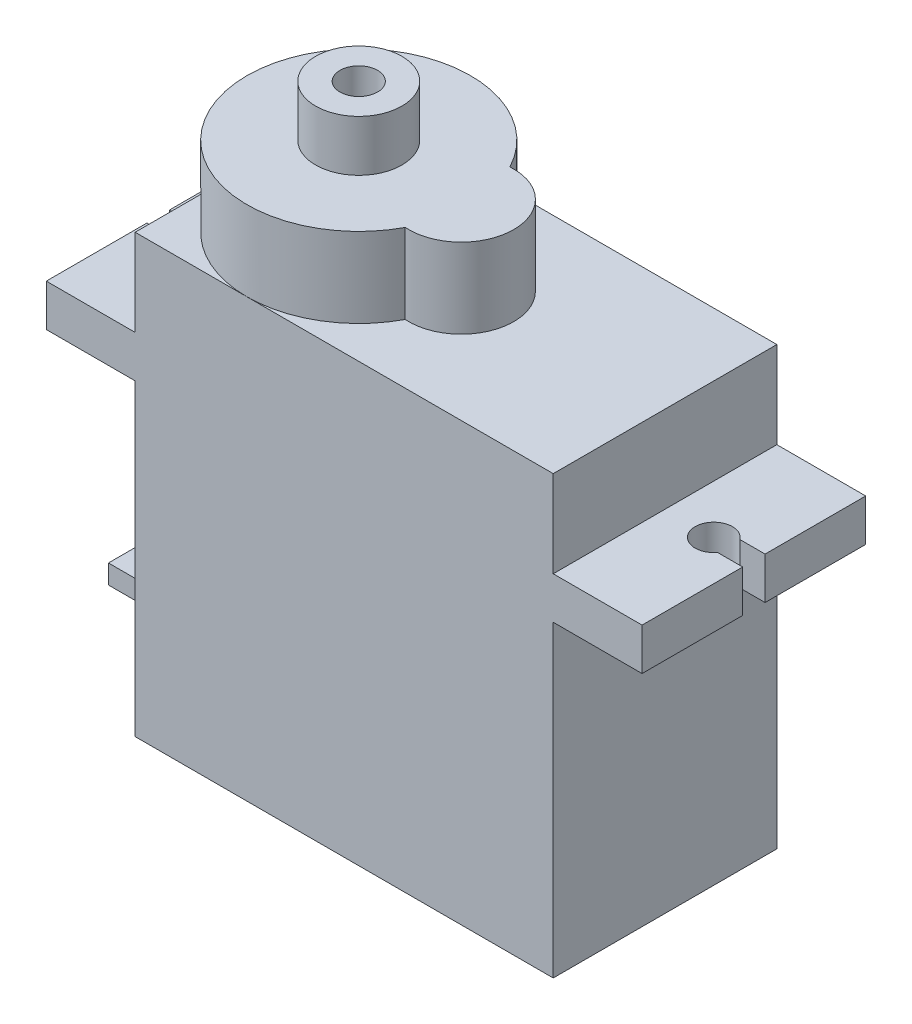
SolidWorks part; units mm, degrees
ref_plane "Front Plane" through (0, 0, 0) normal (0, 0, 1) x (1, 0, 0)
ref_plane "Top Plane" through (0, 0, 0) normal (0, 1, 0) x (1, 0, 0)
ref_plane "Right Plane" through (0, 0, 0) normal (1, 0, 0) x (0, 0, -1)
sketch "Sketch1" plane through (0, 0, 0) normal (0, 1, 0) x (1, 0, 0)
  line L1 (0, 0) -> (22.7711, 0)
  line L2 (0, 0) -> (0, 12.18)
  line L3 (0, 12.18) -> (22.7711, 12.18)
  line L4 (22.7711, 0) -> (22.7711, 12.18)
  dimension "D1" = 12.18
  dimension "D2" = 22.7711
extrude "Boss-Extrude1" add sketch "Sketch1" along normal blind 23.79
ref_plane "Plane1" through (0, 19.0656, 0) normal (0, 1, 0) x (1, 0, 0)
sketch "Sketch3" plane through (0, 19.0656, 0) normal (0, 1, 0) x (1, 0, 0)
  line L0 (22.7711, 12.18) -> (0, 12.18) construction
  line L1 (-4.8387, 0) -> (27.6098, 0)
  line L2 (-4.8387, 0) -> (-4.8387, 12.18)
  line L3 (-4.8387, 12.18) -> (27.6098, 12.18)
  line L4 (27.6098, 0) -> (27.6098, 12.18)
  line L5 (0, 0) -> (22.7711, 0) construction
  point P6 (11.3856, 0)
  point P9 (11.3856, 0)
  dimension "D1" = 32.4485
extrude "Boss-Extrude2" add sketch "Sketch3" against normal blind 2.286
sketch "Sketch4" plane through (0, 19.0656, 0) normal (0, 1, 0) x (1, 0, 0)
  line L0 (-3.4671, 6.6996) -> (-3.4671, 5.4804) construction
  line L1 (-4.8387, 6.6996) -> (-3.4671, 6.6996)
  line L2 (-4.8387, 12.18) -> (-4.8387, 0) construction
  line L3 (-3.4671, 5.4804) -> (-4.8387, 5.4804)
  line L4 (-1.6383, 6.09) -> (-1.6383, 8.3545) construction
  line L5 (11.3856, 12.18) -> (11.3856, 0) construction
  line L6 (22.7711, 12.18) -> (0, 12.18) construction
  line L7 (0, 0) -> (22.7711, 0) construction
  line L8 (24.4094, 6.09) -> (24.4094, 8.3545) construction
  line L9 (26.2382, 6.6996) -> (26.2382, 5.4804) construction
  line L10 (26.2382, 5.4804) -> (27.6098, 5.4804)
  line L11 (27.6098, 6.6996) -> (26.2382, 6.6996)
  line L12 (-4.8387, 6.6996) -> (-4.8387, 5.4804)
  line L13 (27.6098, 6.6996) -> (27.6098, 5.4804)
  arc A0 (-3.4671, 6.6996) -> (-3.4671, 5.4804) centre (-2.6543, 6.09) cw
  arc A1 (26.2382, 6.6996) -> (26.2382, 5.4804) centre (25.4254, 6.09) ccw
  point P6 (-3.4671, 6.09)
  point P8 (-4.8387, 6.09)
  dimension "D1" = 1.016
  dimension "D2" = 3.2004
  dimension "D3" = 1.2192
extrude "Cut-Extrude1" cut sketch "Sketch4" against normal through all
sketch "Sketch5" plane through (0, 23.79, 0) normal (0, 1, 0) x (1, 0, 0)
  line L0 (22.7711, 12.18) -> (0, 12.18) construction
  line L1 (0, 12.18) -> (0, 0) construction
  line L2 (0, 0) -> (22.7711, 0) construction
  line L3 (14.5288, 6.09) -> (14.5288, 9.2952) construction
  arc A0 (11.4717, 8.9405) -> (11.4717, 3.2395) centre (6.09, 6.09) ccw
  arc A1 (11.4717, 3.2395) -> (11.4717, 8.9405) centre (11.6713, 6.09) ccw
  dimension "D1" = 14.5288
  dimension "D2" = 5.715
extrude "Boss-Extrude3" add sketch "Sketch5" along normal blind 4.3434
sketch "Sketch6" plane through (0, 28.1334, 0) normal (0, 1, 0) x (1, 0, 0)
  circle A0 centre (6.09, 6.09) radius 2.3495
  arc A1 (11.4717, 8.9405) -> (11.4717, 3.2395) centre (6.09, 6.09) ccw construction
  dimension "D1" = 4.699
extrude "Boss-Extrude4" add sketch "Sketch6" along normal blind 2.7813 contours A0
sketch "Sketch7" plane through (0, 0, 0) normal (-1, 0, 0) x (0, 0, 1)
  line L0 (-12.18, 0) -> (0, 0) construction
  line L1 (-7.5378, 1.78) -> (-4.6422, 1.78)
  line L2 (-7.5378, 1.78) -> (-7.5378, 2.8214)
  line L3 (-7.5378, 2.8214) -> (-4.6422, 2.8214)
  line L4 (-4.6422, 1.78) -> (-4.6422, 2.8214)
  point P4 (-6.09, 1.78)
  point P7 (-6.09, 0)
  dimension "D1" = 1.0414
  dimension "D2" = 2.8956
  dimension "D3" = 1.78
extrude "Boss-Extrude5" add sketch "Sketch7" along normal blind 6.096
ref_axis "Axis1" through (6.09, 30.9147, -6.09) along (0, -1, 0)
ref_plane "Plane2" through (6.09, 0, 0) normal (-1, 0, 0) x (0, 0, 1)
sketch "Sketch8" plane through (0, 28.1334, 0) normal (0, 1, 0) x (1, 0, 0)
  circle A0 centre (6.09, 6.09) radius 3.556
  dimension "D1" = 7.112
extrude "Boss-Extrude6" [suppressed] add sketch "Sketch8" along normal blind 4.4577
sketch "Sketch9" [suppressed] plane through (0, 31.9532, 0) normal (0, 1, 0) x (1, 0, 0)
  line L0 (2.5019, 6.0579) -> (3.8735, 18.5674)
  line L1 (3.8735, 18.5674) -> (8.2423, 18.5674)
  line L2 (8.2423, 18.5674) -> (9.6139, 6.0579)
  line L3 (6.0579, 6.0579) -> (6.0579, 18.5674) construction
  line L4 (2.5019, 6.0579) -> (9.6139, 6.0579)
  line L5 (8.9281, 12.3127) -> (6.0579, 12.3127) construction
  line L6 (6.0579, 12.3127) -> (3.1877, 12.3127) construction
  circle A0 centre (6.0579, 6.0579) radius 3.556 construction
  point P10 (6.0579, 18.5674)
  point P18 (6.0579, 2.5019)
  dimension "D1" = 4.3688
  dimension "D2" = 16.0655
extrude "Boss-Extrude7" [suppressed] add sketch "Sketch9" against normal blind 1.651
sketch "Sketch11" [suppressed] plane through (0, 31.9532, 0) normal (0, 1, 0) x (1, 0, 0)
  circle A0 centre (6.0579, 6.0579) radius 2.4257
  arc A1 (2.5864, 6.8284) -> (9.5294, 6.8284) centre (6.0579, 6.0579) ccw construction
  dimension "D1" = 4.8514
extrude "Cut-Extrude2" [suppressed] cut sketch "Sketch11" against normal blind 2.54
sketch "Sketch12" [suppressed] plane through (0, 29.4132, 0) normal (0, 1, 0) x (1, 0, 0)
  circle A0 centre (6.0579, 6.0579) radius 1.2001
  dimension "D1" = 2.4003
extrude "Cut-Extrude3" [suppressed] cut sketch "Sketch12" against normal up to surface (1.9177 mm away)
hole_wizard "M2.5x0.45 Tapped Hole1" positions "Sketch14" profile "Sketch15" tap size "M2.5x0.45" standard "ANSI Metric"
sketch "Sketch14" plane through (0, 30.9147, 0) normal (0, 1, 0) x (1, 0, 0)
  point P0 (6.09, 6.09)
sketch "Sketch15" plane through (6.09, 30.9147, -6.09) normal (1, 0, 0) x (0, 0, 1)
  line L0 (0, 0) -> (0, 4.6159)
  line L1 (0, 4.6159) -> (1.025, 4)
  line L2 (1.025, 4) -> (1.025, 0)
  line L5 (1.025, 0) -> (0, 0)
  line L10 (0, 4.6159) -> (-1.025, 4) construction
  line L11 (0, -6.35) -> (0, 107.95) construction
  dimension "Tap Drill Dia." = 2.05
  dimension "Tap Drill Depth" = 4
  dimension "Drill Angle" = 118
cosmetic thread "Hole Thread1" parameters "D1"=4, "D2"=2.5
